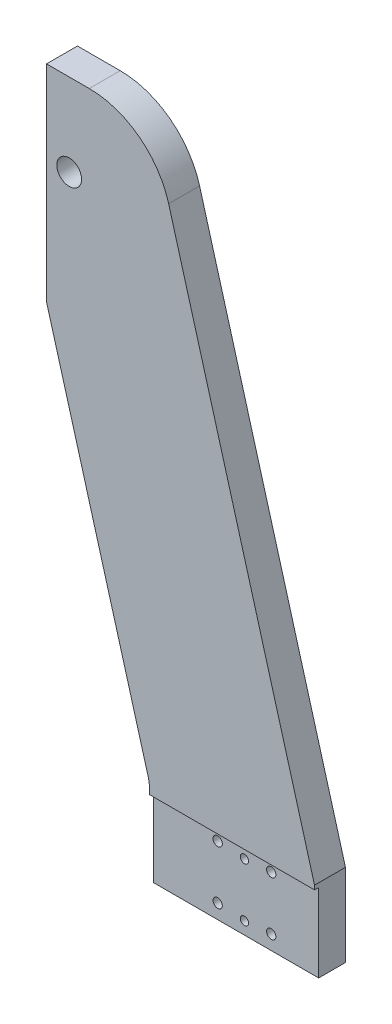
SolidWorks part; units mm, degrees
ref_plane "Alzado" through (0, 0, 0) normal (0, 0, 1) x (1, 0, 0)
ref_plane "Planta" through (0, 0, 0) normal (0, 1, 0) x (1, 0, 0)
ref_plane "Vista lateral" through (0, 0, 0) normal (1, 0, 0) x (0, 0, -1)
sketch "Croquis1" plane through (0, 0, 0) normal (0, 0, 1) x (1, 0, 0)
  line L0 (80, 0) -> (80, 40)
  line L1 (-50, 320) -> (-29.2688, 320)
  line L2 (-50, 320) -> (-50, 220)
  line L3 (0, 0) -> (80, 0)
  line L4 (9.2285, 290.8607) -> (80, 40)
  line L9 (-50, 220) -> (-0.7513, 45.4303)
  line L11 (0, 40) -> (0, 0)
  arc A2 (9.2285, 290.8607) -> (-29.2688, 320) centre (-29.2688, 280) ccw
  arc A3 (-0.7513, 45.4303) -> (0, 40) centre (-20, 40) cw
  dimension "D7" = 40
  dimension "D9" = 40
  dimension "D4" = 20
  dimension "D1" = 50
  dimension "D2" = 320
  dimension "D3" = 80
  dimension "D5" = 100
  dimension "D6" = 40
extrude "Saliente-Extruir1" add sketch "Croquis1" along normal blind 15
sketch "Croquis2" plane through (0, 0, 0) normal (0, 0, -1) x (-1, 0, 0)
  line L0 (29.2688, 320) -> (50, 320) construction
  line L2 (50, 320) -> (50, 220) construction
  circle A0 centre (39, 280) radius 6
  dimension "D3" = 12
  dimension "D1" = 40
  dimension "D2" = 11
extrude "Cortar-Extruir1" cut sketch "Croquis2" against normal through all
hole_wizard "Perforador para roscar para macho de roscar para M44" positions "Croquis7" profile "Croquis8" hole size "M4" standard "DIN"
sketch "Croquis7" plane through (0, 0, 0) normal (0, 0, -1) x (-1, 0, 0)
  line L0 (39, 298.25) -> (39, 261.75)
  circle A0 centre (39, 280) radius 6 construction
  point P10 (39, 298.25)
  point P12 (39, 261.75)
  dimension "D1" = 18.25
  dimension "D2" = 18.25
sketch "Croquis8" plane through (-39, 261.75, 0) normal (1, 0, 0) x (0, 1, 0)
  line L0 (0, 0) -> (0, 7.9914)
  line L1 (0, 7.9914) -> (1.65, 7)
  line L2 (1.65, 7) -> (1.65, 0)
  line L5 (1.65, 0) -> (0, 0)
  line L10 (0, 7.9914) -> (-1.65, 7) construction
  line L11 (0, -6.35) -> (0, 107.95) construction
  dimension "Diámetro de taladro" = 3.3
  dimension "Profundidad de taladro" = 7
  dimension "Ángulo de perforador" = 118
sketch "Croquis9" plane through (0, 0, 15) normal (0, 0, 1) x (1, 0, 0)
  line L1 (0, 0) -> (80, 0)
  line L2 (0, 0) -> (0, 38)
  line L3 (0, 38) -> (80, 38)
  line L4 (80, 0) -> (80, 38)
  dimension "D1" = 80
  dimension "D2" = 38
extrude "Cortar-Extruir2" cut sketch "Croquis9" against normal blind 2
hole_wizard "Taladros de espiga de Ø4.0mm1" positions "Croquis10" profile "Croquis12" hole size "Ø4.0" standard "DIN"
sketch "Croquis10" plane through (-50, 0, 0) normal (-1, 0, 0) x (0, 0, 1)
  line L0 (0, 320) -> (0, 220) construction
  line L1 (15, 320) -> (0, 320) construction
  point P0 (6, 294)
  point P2 (6, 266)
  dimension "D1" = 6
  dimension "D2" = 6
  dimension "D3" = 26
  dimension "D4" = 54
sketch "Croquis12" plane through (-50, 294, 6) normal (0, 1, 0) x (0, 0, 1)
  line L0 (0, 0) -> (0, 18.2017)
  line L1 (0, 18.2017) -> (2, 17)
  line L2 (2, 17) -> (2, 0)
  line L5 (2, 0) -> (0, 0)
  line L10 (0, 18.2017) -> (-2, 17) construction
  line L11 (0, -6.35) -> (0, 107.95) construction
  dimension "Diámetro de taladro" = 4
  dimension "Profundidad de taladro" = 17
  dimension "Ángulo de perforador" = 118
hole_wizard "Taladro roscado M41" positions "Croquis13" profile "Croquis14" tap size "M4" standard "DIN"
sketch "Croquis13" plane through (-50, 0, 0) normal (-1, 0, 0) x (0, 0, 1)
  line L0 (0, 320) -> (0, 220) construction
  line L1 (15, 320) -> (0, 320) construction
  point P0 (6, 305)
  point P2 (6, 255)
  dimension "D1" = 6
  dimension "D2" = 6
  dimension "D3" = 15
  dimension "D4" = 65
sketch "Croquis14" plane through (-50, 305, 6) normal (0, 1, 0) x (0, 0, 1)
  line L0 (0, 0) -> (0, 12.4914)
  line L1 (0, 12.4914) -> (1.65, 11.5)
  line L2 (1.65, 11.5) -> (1.65, 0)
  line L5 (1.65, 0) -> (0, 0)
  line L10 (0, 12.4914) -> (-1.65, 11.5) construction
  line L11 (0, -6.35) -> (0, 107.95) construction
  dimension "Diámetro de perforador para roscar" = 3.3
  dimension "Profundidad de perforador para roscar" = 11.5
  dimension "Ángulo de perforador" = 118
cosmetic thread "Rosca de taladro1" parameters "D1"=8, "D2"=4
cosmetic thread "Rosca de taladro2" parameters "D1"=8, "D2"=4
hole_wizard "Refrentado para tornillo con cabeza hueca de M41" positions "Croquis15" profile "Croquis16" counterbore size "M4" standard "DIN" end condition through all
sketch "Croquis15" plane through (0, 0, 0) normal (0, 0, -1) x (-1, 0, 0)
  line L1 (-57, 7) -> (-31, 7)
  line L2 (-57, 7) -> (-57, 33)
  line L3 (-57, 33) -> (-31, 33)
  line L4 (-31, 7) -> (-31, 33)
  line L5 (-57, 7) -> (-31, 33) construction
  line L6 (-57, 33) -> (-31, 7) construction
  line L16 (0, 0) -> (-80, 0) construction
  line L17 (-80, 0) -> (-80, 40) construction
  point P148 (-57, 33)
  point P151 (-31, 33)
  point P154 (-31, 7)
  point P157 (-57, 7)
  dimension "D1" = 26
  dimension "D2" = 26
  dimension "D3" = 23
  dimension "D4" = 7
sketch "Croquis16" plane through (57, 7, 0) normal (1, 0, 0) x (0, 1, 0)
  line L0 (0, 0) -> (0, 15)
  line L1 (0, 15) -> (2.25, 15)
  line L3 (2.25, 15) -> (2.25, 4.4)
  line L4 (2.25, 4.4) -> (4, 4.4)
  line L5 (4, 4.4) -> (4, 0)
  line L7 (4, 0) -> (0, 0)
  line L11 (0, -6.35) -> (0, 107.95) construction
  dimension "Diámetro de taladro hasta el siguiente" = 4.5
  dimension "Profundidad de taladro hasta el siguiente" = 15
  dimension "Diámetro de refrentado" = 8
  dimension "Profundidad de refrentado" = 4.4
hole_wizard "Taladros de espiga de Ø4.0mm2" positions "Croquis17" profile "Croquis18" hole size "Ø4.0" standard "DIN" end condition through all
sketch "Croquis17" plane through (0, 0, 0) normal (0, 0, -1) x (-1, 0, 0)
  line L0 (-44, 32) -> (-44, 6) construction
  line L2 (0, 0) -> (-80, 0) construction
  line L3 (-80, 0) -> (-80, 40) construction
  point P0 (-44, 32)
  point P2 (-44, 6)
  dimension "D1" = 26
  dimension "D2" = 6
  dimension "D3" = 36
sketch "Croquis18" plane through (44, 32, 0) normal (1, 0, 0) x (0, 1, 0)
  line L0 (0, 0) -> (0, 15)
  line L1 (0, 15) -> (2, 15)
  line L2 (2, 15) -> (2, 0)
  line L5 (2, 0) -> (0, 0)
  line L11 (0, -6.35) -> (0, 107.95) construction
  dimension "Diámetro de taladro hasta el siguiente" = 4
  dimension "Profundidad de taladro hasta el siguiente" = 15
